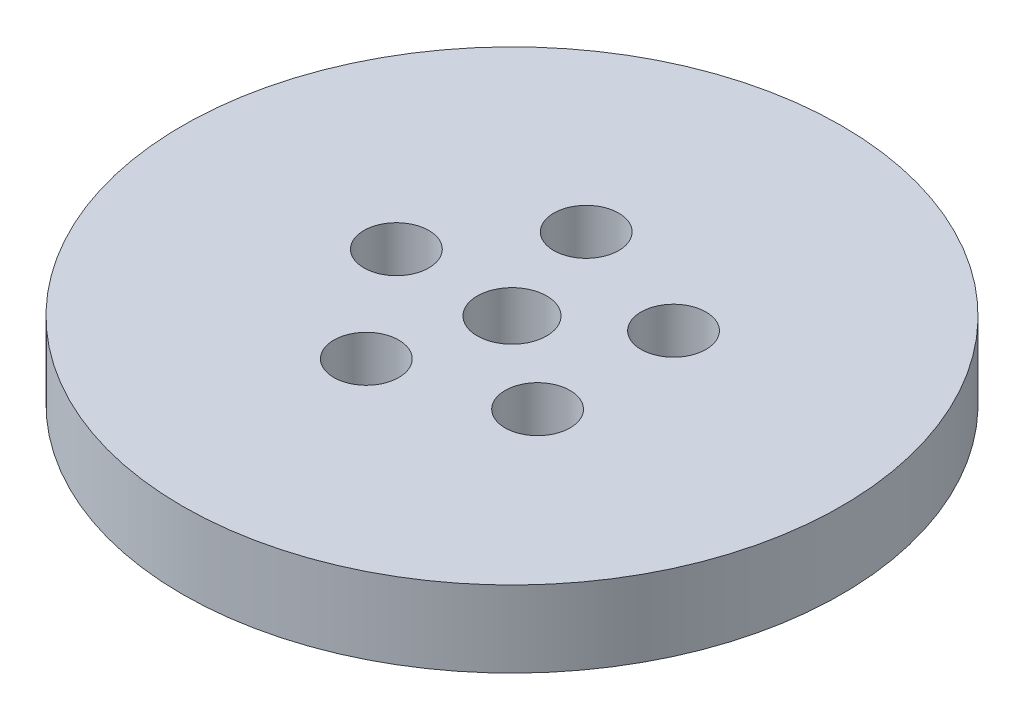
SolidWorks part; units mm, degrees
ref_plane "Front Plane" through (0, 0, 0) normal (0, 0, 1) x (1, 0, 0)
ref_plane "Top Plane" through (0, 0, 0) normal (0, 1, 0) x (1, 0, 0)
ref_plane "Right Plane" through (0, 0, 0) normal (1, 0, 0) x (0, 0, -1)
sketch "Sketch1" plane through (0, 0, 0) normal (0, 1, 0) x (1, 0, 0)
  circle A0 centre (0, 0) radius 95
  dimension "FLANGE_OD" = 190
extrude "Boss-Extrude1" add sketch "Sketch1" along normal blind 22
sketch "Sketch2" plane through (0, 0, 0) normal (0, 1, 0) x (1, 0, 0)
  circle A0 centre (0, 0) radius 10
  dimension "BORE_D" = 20
extrude "Cut-Extrude1" cut sketch "Sketch2" along normal through all
sketch "Sketch3" plane through (0, 22, 0) normal (0, 1, 0) x (1, 0, 0)
  circle A0 centre (0, 0) radius 33.3282 construction
  circle A1 centre (-33.3282, 0) radius 9.3647
  dimension "BOLT_D" = 18.7295
  dimension "BOLT_PCD" = 66.6563
extrude "Cut-Extrude2" cut sketch "Sketch3" against normal blind 16.1579
pattern_circular "CirPattern1" count 5 over 360 about axis through (0, 0, 0) along (0, 1, 0) of "Cut-Extrude2"
